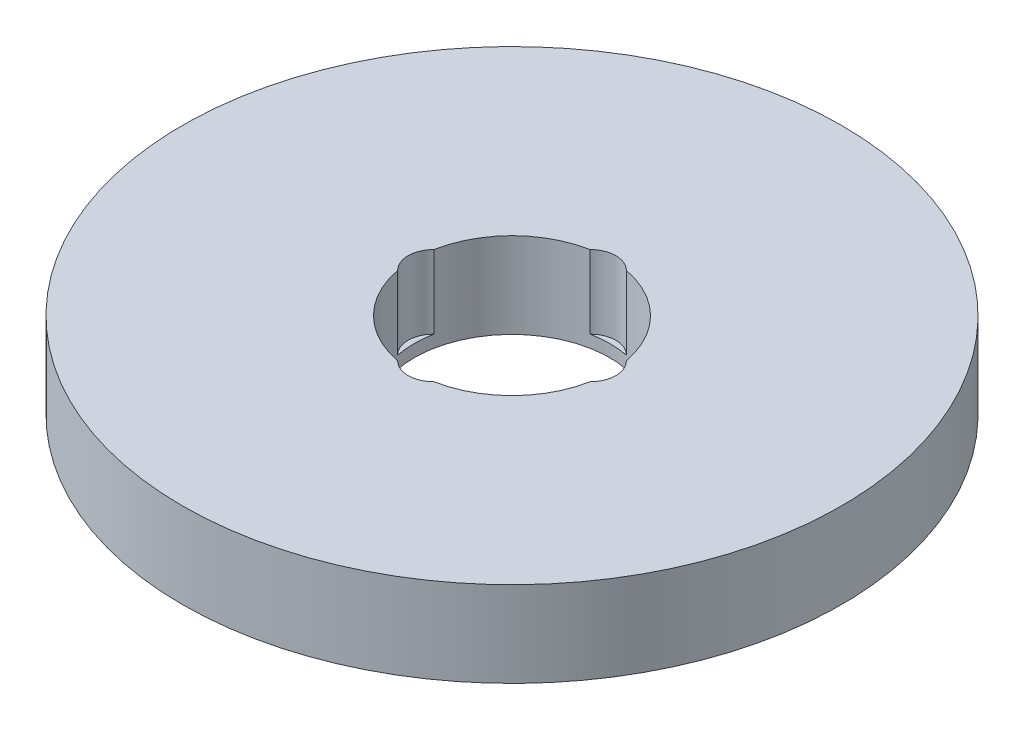
SolidWorks part; units mm, degrees
ref_plane "Front Plane" through (0, 0, 0) normal (0, 0, 1) x (1, 0, 0)
ref_plane "Top Plane" through (0, 0, 0) normal (0, 1, 0) x (1, 0, 0)
ref_plane "Right Plane" through (0, 0, 0) normal (1, 0, 0) x (0, 0, -1)
sketch "Sketch1" plane through (0, 0, 0) normal (0, 1, 0) x (1, 0, 0)
  circle A0 centre (0, 0) radius 92.5
  dimension "FLANGE_OD" = 185
extrude "Boss-Extrude1" add sketch "Sketch1" along normal blind 24
sketch "Sketch2" plane through (0, 0, 0) normal (0, 1, 0) x (1, 0, 0)
  circle A0 centre (0, 0) radius 27.5
  dimension "BORE_D" = 55
extrude "Cut-Extrude1" cut sketch "Sketch2" along normal through all
sketch "Sketch3" plane through (0, 24, 0) normal (0, 1, 0) x (1, 0, 0)
  circle A0 centre (0, 0) radius 22.0384 construction
  circle A1 centre (-22.0384, 0) radius 7.1161
  dimension "BOLT_D" = 14.2323
  dimension "BOLT_PCD" = 44.0768
extrude "Cut-Extrude2" cut sketch "Sketch3" against normal blind 20.559
pattern_circular "CirPattern1" count 4 over 360 about axis through (0, 0, 0) along (0, 1, 0) of "Cut-Extrude2"
